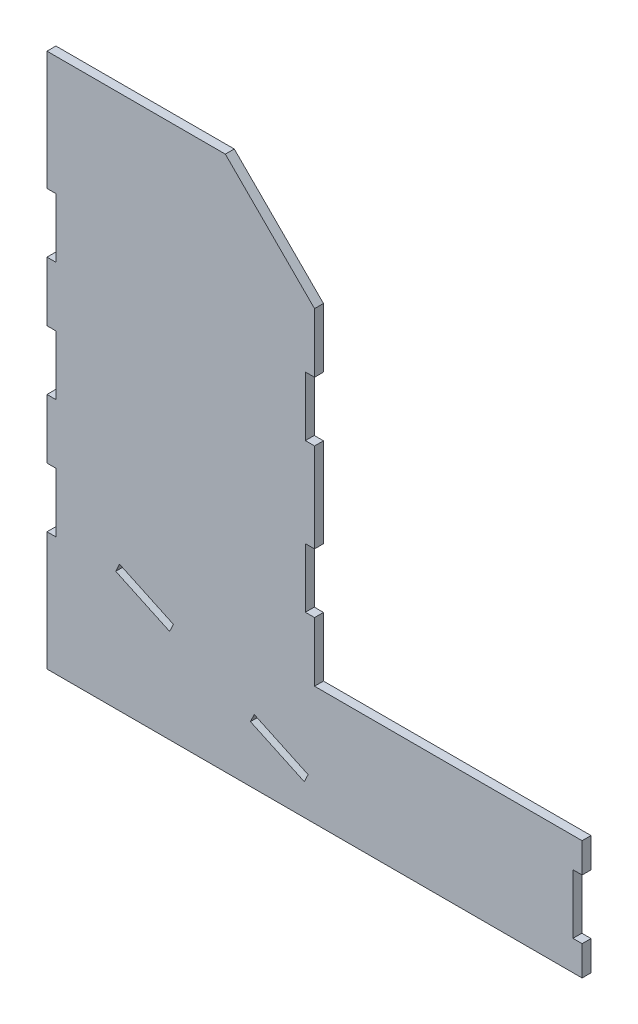
SolidWorks part; units mm, degrees
material "Maple"
ref_plane "Front Plane" through (0, 0, 0) normal (0, 0, 1) x (1, 0, 0)
ref_plane "Top Plane" through (0, 0, 0) normal (0, 1, 0) x (1, 0, 0)
ref_plane "Right Plane" through (0, 0, 0) normal (1, 0, 0) x (0, 0, -1)
sketch "Sketch1" plane through (0, 0, 0) normal (0, 0, 1) x (1, 0, 0)
  line L0 (-93.9149, 114.3977) -> (-93.9149, -65.6023)
  line L1 (-93.9149, -65.6023) -> (86.0851, -65.6023)
  line L2 (86.0851, -65.6023) -> (86.0851, -25.6023)
  line L3 (86.0851, -25.6023) -> (-3.9149, -25.6023)
  line L4 (-3.9149, -25.6023) -> (-3.9149, 84.3977)
  line L5 (-3.9149, 84.3977) -> (-33.9149, 114.3977)
  line L6 (-33.9149, 114.3977) -> (-93.9149, 114.3977)
  line L7 (-92.4149, 114.3977) -> (-92.4149, -65.6023) construction
  line L8 (-92.4149, 74.3977) -> (-92.4149, 54.3977)
  line L9 (-93.9149, 24.3977) -> (-3.9149, 24.3977) construction
  line L10 (-92.4149, 14.3977) -> (-92.4149, 34.3977)
  line L11 (-92.4149, -25.6023) -> (-92.4149, -5.6023)
  line L12 (86.0851, -45.6023) -> (-93.9149, -45.6023) construction
  line L13 (-5.4149, 84.3977) -> (-5.4149, -25.6023) construction
  line L14 (-5.4149, 64.3977) -> (-5.4149, 44.3977)
  line L15 (-5.4149, 29.3977) -> (-19.91, 29.3977) construction
  line L16 (-5.4149, -5.6023) -> (-5.4149, 14.3977)
  line L17 (84.5851, -25.6023) -> (84.5851, -65.6023) construction
  line L18 (84.5851, -35.6023) -> (84.5851, -55.6023)
  point P19 (-92.4149, 24.3977)
  dimension "D1" = 180
  dimension "D2" = 180
  dimension "D3" = 90
  dimension "D5" = 40
  dimension "D6" = 30
  dimension "D4" = 45
  dimension "D7" = 1.5
  dimension "D8" = 0
  dimension "D9" = 0
  dimension "D10" = 20
  dimension "D11" = 20
  dimension "D13" = 20
  dimension "D15" = 1.5
  dimension "D16" = 0
  dimension "D17" = 0
  dimension "D19" = 30
  dimension "D20" = 1.5
  dimension "D21" = 0
  dimension "D22" = 0
extrude "Boss-Extrude1" add sketch "Sketch1" along normal mid plane 3 contours L5 L6 L0 L1 L2 L3 L4 region at (-32.9847, 9.514, 0)
extrude "Cut-Extrude-Thin1" cut sketch "Sketch1<3>" against normal through all both and the other way through all thin contours L8 | L10 | L11 | L14 | L16 | L18 thin type mid plane wall 3.18
sketch "Sketch1<3>" plane through (0, 0, 0) normal (0, 0, 1) x (1, 0, 0) same geometry as "Sketch1"
fillet "Fillet2" [suppressed] radius 4
sketch "Sketch2" plane through (0, 0, 1.5) normal (0, 0, 1) x (1, 0, 0)
  line L1 (-25.4733, -46.6976) -> (-7.3472, -55.1499) construction
  line L3 (-7.3472, -55.1499) -> (-6.0793, -52.431) construction
  line L5 (-6.0793, -52.431) -> (-24.2055, -43.9786) construction
  line L7 (-24.2055, -43.9786) -> (-25.4733, -46.6976) construction
  line L21 (-51.3947, -31.3001) -> (-69.5209, -22.8477) construction
  line L23 (-69.5209, -22.8477) -> (-70.7887, -25.5667) construction
  line L25 (-70.7887, -25.5667) -> (-52.6626, -34.019) construction
  line L27 (-52.6626, -34.019) -> (-51.3947, -31.3001) construction
  line L40 (-25.4733, -46.6976) -> (-7.3472, -55.1499)
  line L41 (-7.3472, -55.1499) -> (-6.0793, -52.431)
  line L42 (-6.0793, -52.431) -> (-24.2055, -43.9786)
  line L43 (-24.2055, -43.9786) -> (-25.4733, -46.6976)
  line L44 (-51.3947, -31.3001) -> (-69.5209, -22.8477)
  line L45 (-69.5209, -22.8477) -> (-70.7887, -25.5667)
  line L46 (-70.7887, -25.5667) -> (-52.6626, -34.019)
  line L47 (-52.6626, -34.019) -> (-51.3947, -31.3001)
extrude "Cut-Extrude1" cut sketch "Sketch2" against normal up to next
equation "\"D7@Sketch1\"= \"lateral offset@tower.Assembly\""
equation "\"D8@Sketch1\" = \"vertical offset@tower.Assembly\""
equation "\"D9@Sketch1\"= \"vertical offset@tower.Assembly\""
equation "\"D13@Sketch1\"=\"D10@Sketch1\""
equation "\"D11@Sketch1\"=\"D10@Sketch1\""
equation "\"D1@Boss-Extrude1\" = \"T@tower.Assembly\""
equation "\"D15@Sketch1\"=\"D7@Sketch1\""
equation "\"D16@Sketch1\"=\"D8@Sketch1\""
equation "\"D17@Sketch1\"=\"D8@Sketch1\""
equation "\"D20@Sketch1\"=\"D7@Sketch1\""
equation "\"D21@Sketch1\"=\"D8@Sketch1\""
equation "\"D22@Sketch1\"=\"D8@Sketch1\""
equation "\"D2@Sketch1\"=\"D3@Sketch1\"*2"
equation "\"D3@Sketch1\"=\"width@tower.Assembly\""
equation "\"D1@Sketch1\"=2*\"width@tower.Assembly\""
equation "\"D10@Sketch1\"=\"fingers@tower.Assembly\""
